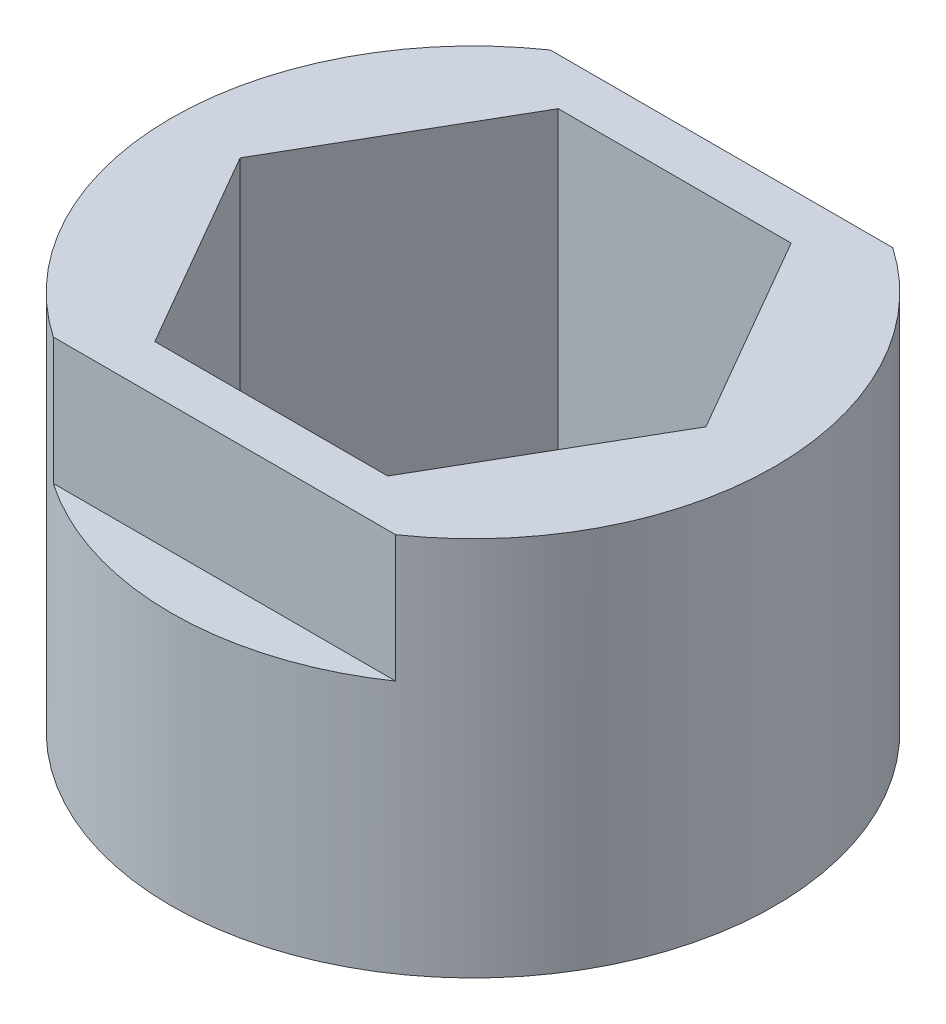
SolidWorks part; units mm, degrees
material "Polyester Resin"
ref_plane "Front Plane" through (0, 0, 0) normal (0, 0, 1) x (1, 0, 0)
ref_plane "Top Plane" through (0, 0, 0) normal (0, 1, 0) x (1, 0, 0)
ref_plane "Right Plane" through (0, 0, 0) normal (1, 0, 0) x (0, 0, -1)
sketch "Sketch1" plane through (0, 0, 0) normal (0, 1, 0) x (1, 0, 0)
  line L1 (-2.9156, 5.05) -> (-5.8312, 0)
  line L2 (-5.8312, 0) -> (-2.9156, -5.05)
  line L3 (-2.9156, -5.05) -> (2.9156, -5.05)
  line L4 (2.9156, -5.05) -> (5.8312, 0)
  line L5 (5.8312, 0) -> (2.9156, 5.05)
  line L6 (2.9156, 5.05) -> (-2.9156, 5.05)
  circle A0 centre (0, 0) radius 5.05 construction
  circle A1 centre (0, 0) radius 7.5565
  dimension "D2" = 15.113
  dimension "D1" = 10.1
extrude "Boss-Extrude1" add sketch "Sketch1" along normal blind 8.89
sketch "Sketch2" plane through (0, 0, 0) normal (0, -1, 0) x (1, 0, 0)
  circle A0 centre (0, 0) radius 7.5565
  circle A1 centre (0, 0) radius 3.3
  dimension "D1" = 6.6
extrude "Boss-Extrude2" add sketch "Sketch2" along normal blind 0.635
sketch "Sketch3" plane through (0, 0, 0) normal (1, 0, 0) x (0, 0, -1)
  line L0 (-6.223, 9.525) -> (-6.223, 5.715)
  line L1 (6.223, 9.525) -> (6.223, 5.715)
  line L2 (-7.5565, -0.635) -> (7.5565, -0.635) construction
  line L3 (-6.223, 9.525) -> (-8.202, 9.525)
  line L4 (-8.202, 9.525) -> (-8.202, 5.715)
  line L5 (-8.202, 5.715) -> (-6.223, 5.715)
  line L6 (6.223, 9.525) -> (8.4791, 9.525)
  line L7 (8.4791, 9.525) -> (8.4791, 5.715)
  line L8 (8.4791, 5.715) -> (6.223, 5.715)
  dimension "D1" = 12.446
  dimension "D2" = 6.223
  dimension "D3" = 3.81
  dimension "D4" = 3.81
  dimension "D5" = 6.35
  dimension "D6" = 6.35
extrude "Cut-Extrude1" cut sketch "Sketch3" against normal through all and the other way through all
equation "\"AB_Central_Bushing_Length\" = .75in"
equation "\"Solid_Length\" = .025in"
equation "\"Hex_Length\" = 0.35"
equation "\"D1@Boss-Extrude1\"= \"Hex_Length\""
equation "\"D1@Boss-Extrude2\"=\"Solid_Length\""
equation "\"Cutout_Angle\" = 80"
